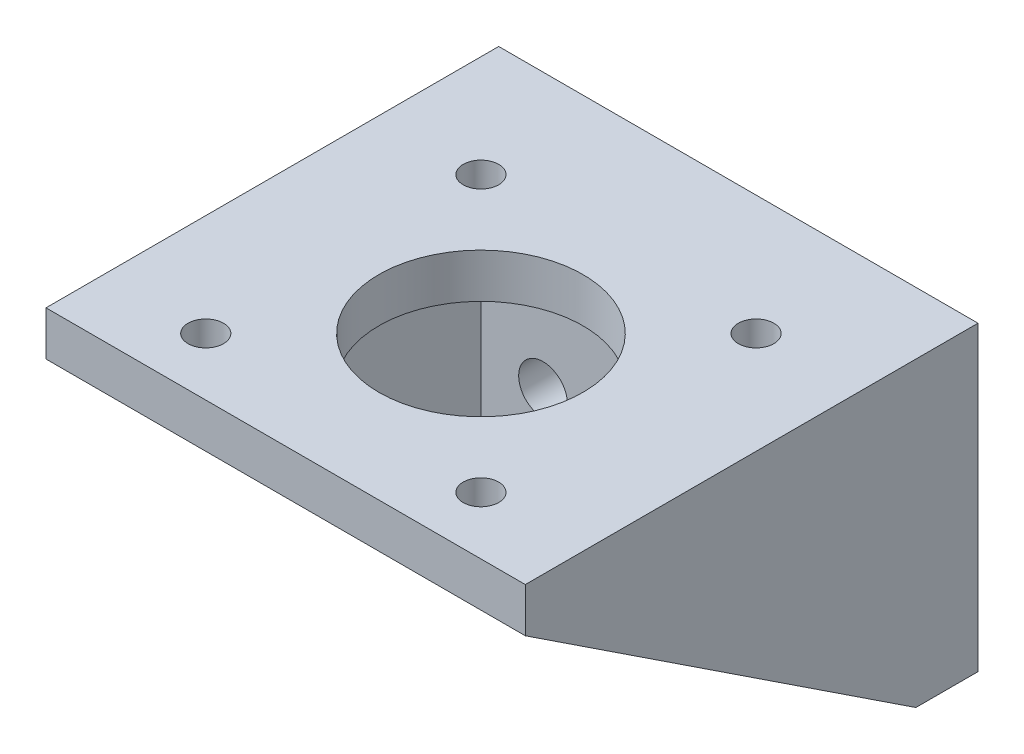
SolidWorks part; units mm, degrees
ref_plane "Front Plane" through (0, 0, 0) normal (0, 0, 1) x (1, 0, 0)
ref_plane "Top Plane" through (0, 0, 0) normal (0, 1, 0) x (1, 0, 0)
ref_plane "Right Plane" through (0, 0, 0) normal (1, 0, 0) x (0, 0, -1)
sketch "Sketch2" plane through (0, 0, 0) normal (0, 1, 0) x (1, 0, 0)
  line L1 (0, 0) -> (44, 0)
  line L2 (0, 0) -> (0, 44)
  line L3 (0, 44) -> (44, 44)
  line L4 (44, 0) -> (44, 44)
  circle A0 centre (6.5, 37.5) radius 2
  circle A1 centre (6.5, 6.5) radius 2
  circle A2 centre (37.5, 6.5) radius 2
  circle A3 centre (37.5, 37.5) radius 2
  circle A4 centre (22, 22) radius 11.5
  point P7 (0, 0)
  point P14 (0, 0)
  dimension "D2" = 4
  dimension "D10" = 23
  dimension "D12" = 22
  dimension "D1" = 44
  dimension "D3" = 31
  dimension "D4" = 31
  dimension "D5" = 31
  dimension "D6" = 31
  dimension "D7" = 31
  dimension "D8" = 6.5
  dimension "D9" = 6.5
  dimension "D11" = 22
extrude "Boss-Extrude1" add sketch "Sketch2" along normal blind 5
sketch "Sketch4" plane through (0, 0, -44) normal (0, 0, -1) x (-1, 0, 0)
  line L1 (-44, 5) -> (0, 5)
  line L2 (-44, 5) -> (-44, -29)
  line L3 (-44, -29) -> (0, -29)
  line L4 (0, 5) -> (0, -29)
  circle A0 centre (-37, -19) radius 2.75
  circle A1 centre (-7, -19) radius 2.75
  dimension "D3" = 5.5
  dimension "D4" = 5.5
  dimension "D1" = 34
  dimension "D2" = 44
  dimension "D5" = 10
  dimension "D6" = 10
  dimension "D7" = 30
  dimension "D8" = 7
extrude "Boss-Extrude2" add sketch "Sketch4" along normal blind 7
sketch "Sketch5" plane through (44, 0, 0) normal (1, 0, 0) x (0, 0, -1)
  line L0 (0, 5) -> (51, 5)
  line L1 (51, 5) -> (51, -29)
  line L2 (51, -29) -> (44, -29)
  line L3 (44, -29) -> (0, 0)
  line L4 (0, 0) -> (0, 5)
extrude "Boss-Extrude3" add sketch "Sketch5" along normal blind 5
sketch "Sketch6" plane through (0, 0, 0) normal (-1, 0, 0) x (0, 0, 1)
  line L0 (-51, 5) -> (0, 5)
  line L1 (0, 5) -> (0, 0)
  line L2 (0, 0) -> (-44, -29)
  line L3 (-44, -29) -> (-51, -29)
  line L4 (-51, -29) -> (-51, 5)
extrude "Boss-Extrude4" add sketch "Sketch6" along normal blind 5
